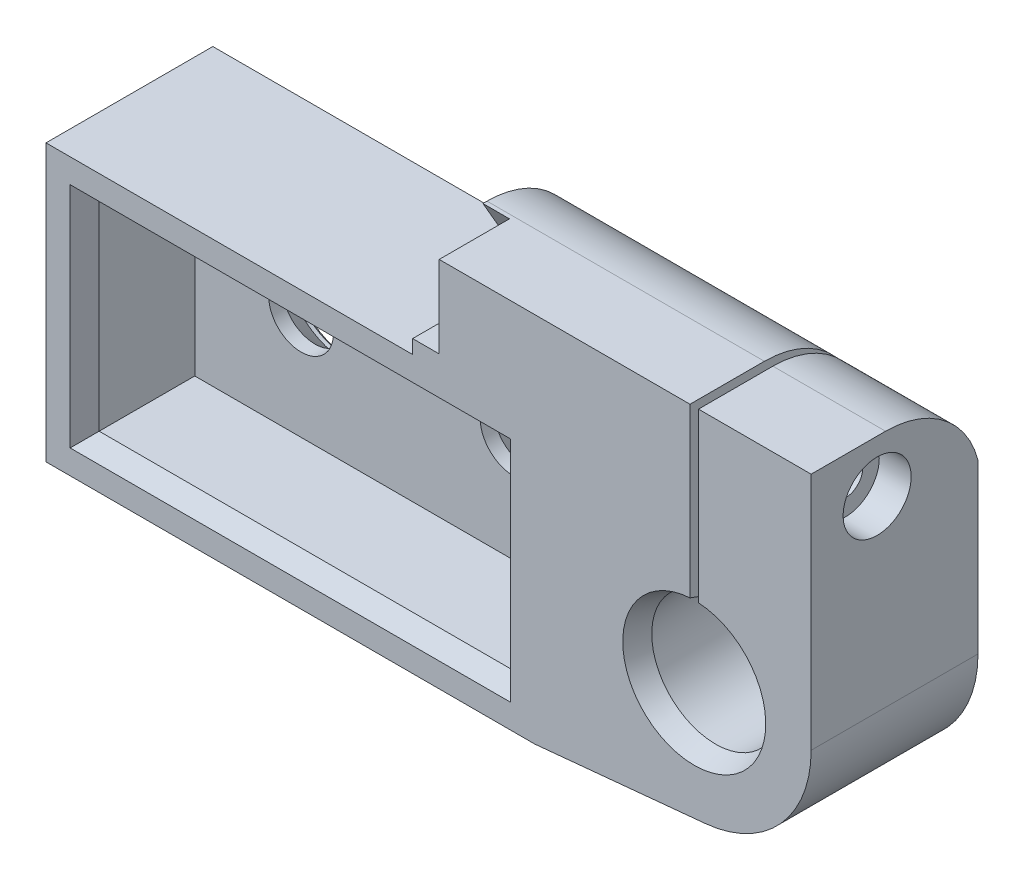
SolidWorks part; units mm, degrees
material "Custom Plastic"
ref_plane "Front Plane" through (0, 0, 0) normal (0, 0, 1) x (1, 0, 0)
ref_plane "Top Plane" through (0, 0, 0) normal (0, 1, 0) x (1, 0, 0)
ref_plane "Right Plane" through (0, 0, 0) normal (1, 0, 0) x (0, 0, -1)
sketch "Sketch1" plane through (0, 0, 0) normal (0, 0, 1) x (1, 0, 0)
  line L0 (-58, 10.5) -> (-18, -9.5) construction
  line L1 (-18, 10.5) -> (-58, 10.5) construction
  line L2 (-18, 10.5) -> (-18, -9.5) construction
  line L3 (-18, -9.5) -> (-58, -9.5) construction
  line L4 (-58, 10.5) -> (-58, -9.5) construction
  line L5 (-58, -9.5) -> (-18, 10.5) construction
  line L6 (-61, 13.5) -> (-61, -12.5)
  line L7 (-15, 13.5) -> (-61, 13.5) construction
  line L8 (-15, 13.5) -> (1.7126, 10.8659) construction
  line L10 (-48, 0.5) -> (-28, 0.5) construction
  line L11 (-61, -12.5) -> (-15, -12.5)
  line L12 (-15, -12.5) -> (-61, -12.5) construction
  line L13 (-15, 13.5) -> (-15, -12.5) construction
  line L14 (-15, -12.5) -> (1.0575, -10.949)
  line L15 (11, 0) -> (11, 22.5)
  line L16 (11, 22.5) -> (-26.5, 22.5)
  line L17 (-61, 13.5) -> (-26.5, 13.5)
  line L18 (-26.5, 13.5) -> (-26.5, 22.5)
  circle A0 centre (0, 0) radius 6 construction
  arc A1 (1.0575, -10.949) -> (11, 0) centre (0, 0) ccw
  circle A2 centre (-48, 0.5) radius 2.5
  circle A3 centre (-28, 0.5) radius 3.15
  point P11 (0, 0)
  point P12 (-38, 0.5)
  point P13 (9.6881, 0)
  dimension "D3" = 12
  dimension "D4" = 5
  dimension "D8" = 5
  dimension "D10" = 6.3
  dimension "D2" = 20
  dimension "D5" = 38
  dimension "D6" = 0.5
  dimension "D7" = 40
  dimension "D9" = 20
  dimension "D11" = 9
  dimension "D12" = 37.5
  dimension "D1" = 3
extrude "Boss-Extrude1" add sketch "Sketch1" along normal blind 16
sketch "Sketch2" plane through (0, 0, 16) normal (0, 0, 1) x (1, 0, 0)
  line L0 (-61, 13.5) -> (-61, -12.5) construction
  line L1 (-58, 10.5) -> (-18, 10.5)
  line L2 (-58, 10.5) -> (-58, -9.5)
  line L3 (-58, -9.5) -> (-18, -9.5)
  line L4 (-18, 10.5) -> (-18, -9.5)
  line L6 (-61, -12.5) -> (-15, -12.5) construction
  dimension "D1" = 3
  dimension "D2" = 3
  dimension "D3" = 20
  dimension "D4" = 40
extrude "Cut-Extrude1" cut sketch "Sketch2" against normal offset from surface (11 mm away) 5 up to face at (-45.5, 0.5, 0)
fillet "Fillet2" radius 9 1 edges at (-7.75, 22.5, 0)
sketch "Sketch3" plane through (0, 0, 16) normal (0, 0, 1) x (1, 0, 0)
  circle A0 centre (0, 0) radius 6
  dimension "D1" = 12
extrude "Cut-Extrude2" cut sketch "Sketch3" against normal offset from surface (13.5 mm away) 2.5 up to face at (-45.5, 0.5, 0)
sketch "Sketch6" plane through (0, 0, 16) normal (0, 0, 1) x (1, 0, 0)
  line L9 (-0.4, 24.3347) -> (0.4, 24.3347)
  line L10 (-0.4, 24.3347) -> (-0.4, 2.9732)
  line L15 (0.4, 24.3347) -> (0.4, 2.9732)
  line L16 (-0.4, 24.3347) -> (0.4, 2.9732) construction
  line L17 (-0.4, 2.9732) -> (0.4, 24.3347) construction
  arc A1 (-0.4, 2.9732) -> (0.4, 2.9732) centre (0, 0) ccw
  point P3 (0.1507, 0.3705)
  point P6 (0, 13.6539)
  point P7 (-14.5521, 6.3495)
  point P9 (-0.1507, -0.3705)
  point P10 (-15.3521, 5.8112)
  dimension "D4" = 3
  dimension "D3" = 0.8
extrude "Cut-Extrude5" cut sketch "Sketch6" against normal through all
sketch "Sketch7" plane through (0, 0, 0) normal (0, 0, -1) x (-1, 0, 0)
  line L0 (38, 10.5) -> (58, -9.5) construction
  line L1 (58, 10.5) -> (48, 0.5) construction
  line L3 (58, 10.5) -> (18, 10.5) construction
  circle A0 centre (48, 0.5) radius 3.05
  dimension "D1" = 6.1
extrude "Cut-Extrude6" cut sketch "Sketch7" against normal through all
sketch "Sketch8" plane through (0, 0, 16) normal (0, 0, 1) x (1, 0, 0)
  line L0 (-51.5, 9.5) -> (-44.5, 9.5) construction
  line L1 (-48, 9.5) -> (-48, 0.5) construction
  line L2 (-58, 10.5) -> (-18, 10.5) construction
  line L3 (-18, 10.5) -> (-58, 10.5) construction
  line L4 (-48, 12.2222) -> (-51.8111, 8.4111)
  line L5 (-51.8111, 8.4111) -> (-48, 4.6)
  line L6 (-48, 4.6) -> (-44.1889, 8.4111)
  line L7 (-44.1889, 8.4111) -> (-48, 12.2222)
  circle A0 centre (-51.5, 9.5) radius 0.55 construction
  circle A1 centre (-44.5, 9.5) radius 0.55 construction
  circle A2 centre (-48, 8.4111) radius 2.6948 construction
  dimension "D1" = 1.1
  dimension "D2" = 7
  dimension "D3" = 1
  dimension "D4" = 5.9
extrude "Boss-Extrude2" [suppressed] add sketch "Sketch8" against normal up to next
ref_axis "Axis1" through (-48, 0.5, 5) along (0, 0, -1)
pattern_circular "CirPattern1" [suppressed] count 2 over 360 about axis through (-48, 0.5, 5) along (0, 0, -1) of bodies 108
fillet "Fillet1" [suppressed] radius 0.8
chamfer "Chamfer2" distance 2 angle 20 4 edges at (-18, 0.5, 16) (-38, 10.5, 16) (-58, 0.5, 16) (-38, -9.5, 16) first distance on face at (-18, 0.5, 10.5) first distance on face at (-38, 10.5, 10.5) first distance on face at (-58, 0.5, 10.5) first distance on face at (-38, -9.5, 10.5)
sketch "Sketch10" plane through (0, 0, 0) normal (0, 0, -1) x (-1, 0, 0)
  circle A0 centre (28, 0.5) radius 6.1
  circle A1 centre (48, 0.5) radius 6.1
  dimension "D1" = 12.2
extrude "Cut-Extrude8" cut sketch "Sketch10" against normal blind 0.7
chamfer "Chamfer3" distance 3 angle 45 2 edges at (-51.05, 0.5, 0.7) (-31.15, 0.5, 0.7)
chamfer "Chamfer4" distance 0.3 angle 45 11 edges at (0, -3, 0) (-61, 0.5, 0) (-38, -12.5, 0) (-6.9712, -11.7245, 0) (8.1435, -7.3948, 0) (-34.1, 0.5, 0) (-54.1, 0.5, 0) (0.4, 8.2366, 0) (-0.4, 8.2366, 0) (11, 6.75, 0) (-43.75, 13.5, 0) tangent propagation no
sketch "Sketch11" plane through (11, 0, 0) normal (1, 0, 0) x (0, 0, -1)
  line L1 (-16, 13.5) -> (-0.3, 13.5) construction
  circle A0 centre (-9.7903, 17.6) radius 1.65
  circle A1 centre (-9.7903, 17.6) radius 3.1 construction
  point P3 (-9.7903, 14.5)
  dimension "D1" = 3.3
  dimension "D2" = 6.2
  dimension "D3" = 1
extrude "Cut-Extrude9" cut sketch "Sketch11" against normal through all
sketch "Sketch12" plane through (11, 0, 0) normal (1, 0, 0) x (0, 0, -1)
  circle A0 centre (-9.7903, 17.6) radius 3.2
  dimension "D1" = 6.4
extrude "Cut-Extrude10" cut sketch "Sketch12" against normal blind 3
sketch "Sketch13" plane through (11, 0, 0) normal (1, 0, 0) x (0, 0, -1)
  line L0 (-9.3862, 22.5) -> (-16, 22.5)
  line L1 (-6.5571, 17.6) -> (-9.3862, 22.5)
  line L2 (-8.2925, 20.4) -> (-11.4069, 20.4) construction
  line L3 (-11.4069, 20.4) -> (-13.0235, 17.6) construction
  line L4 (-13.0235, 17.6) -> (-11.3764, 14.7471) construction
  line L5 (-16, 14.8) -> (-8.1737, 14.8)
  line L6 (-8.1737, 14.8) -> (-6.5571, 17.6)
  line L8 (-16, 22.5) -> (-16, 14.8)
  line L10 (-16, 0) -> (-16, 22.5) construction
  line L11 (-16, 22.5) -> (-9, 22.5) construction
  circle A0 centre (-9.7903, 17.6) radius 2.8 construction
  dimension "D1" = 5.6
extrude "Cut-Extrude11" cut sketch "Sketch13" against normal through all from offset 35 offset against normal yes
chamfer "Chamfer5" distance 2 angle 20 1 edges at (0, -6, 16) first distance on face at (0, -0.0067, 9.25)
sketch "Sketch14" plane through (11, 0, 0) normal (1, 0, 0) x (0, 0, -1)
  line L0 (-9.7903, 17.6) -> (-10.957, 18.7667)
  line L1 (-10.957, 18.7667) -> (-11.7603, 17.9635)
  line L2 (-11.7603, 17.9635) -> (-11.7603, 17.2365)
  line L3 (-11.7603, 17.2365) -> (-10.957, 16.4333)
  line L4 (-10.957, 16.4333) -> (-9.7903, 17.6)
  circle A0 centre (-9.7903, 17.6) radius 1.65 construction
  point P8 (-11.4403, 17.6)
  dimension "D1" = 0.32
extrude "Cut-Extrude12" cut sketch "Sketch14" against normal through all
equation "\"y-cross-rib-thickness\"=6"
equation "\"y-rib-thickness\"=6"
equation "\"bed-plate-thickness\"=6"
equation "\"x-plate-thickness\"=5"
equation "\"rod-diameter\"=12"
equation "\"t-nut-hole-diameter\"=3"
equation "\"y-plate-thickness\"=5"
equation "\"enclosure-thickness\"=0.6"
equation "\"M3-Clearance\"=3.3"
equation "\"M4-Clearance\"=4.3"
equation "\"M5-Clearance\"=5.3"
equation "\"M6-Clearance\"=6.3"
equation "\"M8-Clearance\"=8.3"
equation "\"623-Bearing-Dia\"=11.2"
